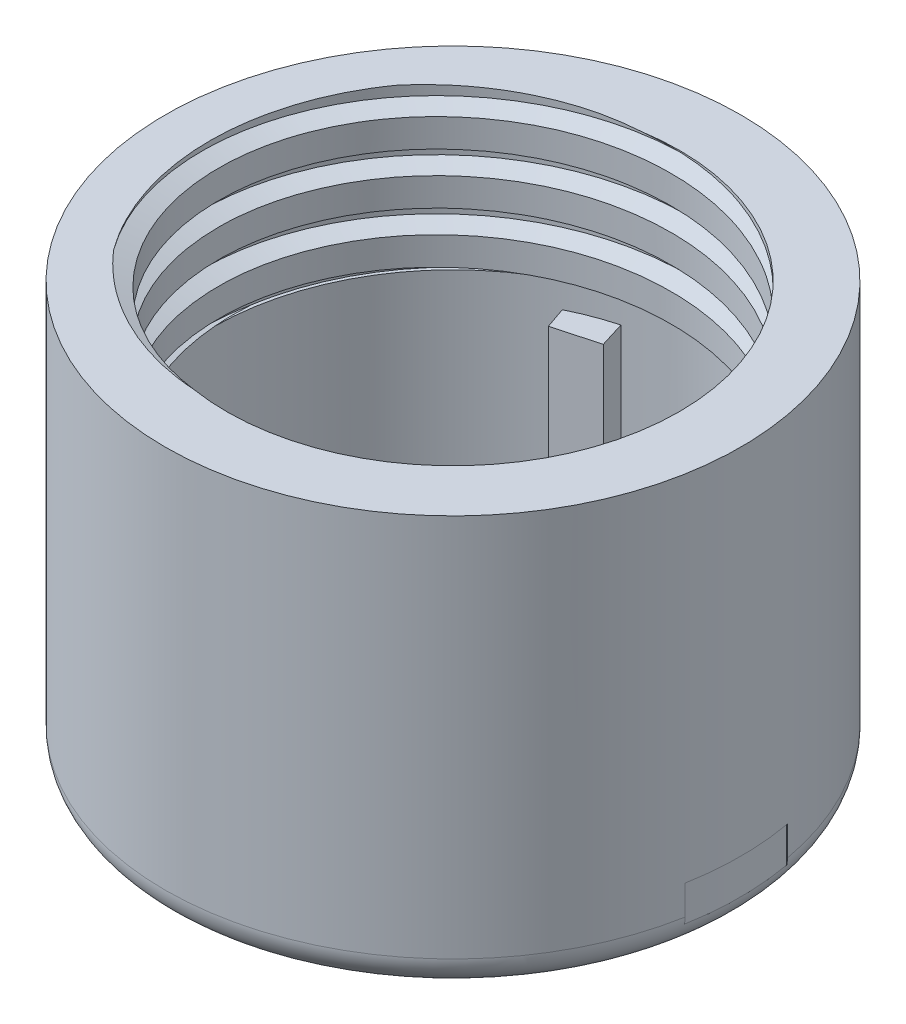
SolidWorks part; units mm, degrees
ref_plane "Front" through (0, 0, 0) normal (0, 0, 1) x (1, 0, 0)
ref_plane "Top" through (0, 0, 0) normal (0, 1, 0) x (1, 0, 0)
ref_plane "Right" through (0, 0, 0) normal (1, 0, 0) x (0, 0, -1)
sketch "Эскиз1" plane through (0, 0, 0) normal (0, 1, 0) x (1, 0, 0)
  circle A0 centre (0, 0) radius 22.5
extrude "Бобышка-Вытянуть1" add sketch "Эскиз1" along normal blind 1
sketch "Эскиз2" plane through (0, 1, 0) normal (0, 1, 0) x (1, 0, 0)
  circle A0 centre (0, 0) radius 22.5
  circle A1 centre (0, 0) radius 17.7
extrude "Бобышка-Вытянуть2" add sketch "Эскиз2" along normal blind 12.5
sketch "Эскиз4" plane through (0, 1, 0) normal (0, 1, 0) x (1, 0, 0)
  circle A0 centre (0, 0) radius 1.5
extrude "Вырез-Вытянуть1" cut sketch "Эскиз4" against normal through all
sketch "Эскиз9" plane through (0, 0, 0) normal (0, -1, 0) x (-1, 0, 0)
  circle A0 centre (0, 0) radius 22.5
  circle A1 centre (0, 0) radius 18.75
extrude "Бобышка-Вытянуть3" add sketch "Эскиз9" along normal blind 17
ref_plane "Плоскость1" through (0, 16.5, 0) normal (0, -1, 0) x (-1, 0, 0)
sketch "Эскиз10" plane through (0, 16.5, 0) normal (0, -1, 0) x (-1, 0, 0)
  circle A0 centre (0, 0) radius 17.7
curve "Спираль1" pitch 4 height 15.5 turns 3.875
sketch "Эскиз11" plane through (0, 16.5, 0) normal (0, -1, 0) x (-1, 0, 0)
  circle A0 centre (0, 0) radius 10 construction
ref_plane "Плоскость2" through (0, 0, 0) normal (-1, 0, 0) x (0, 0, 1)
sketch "Эскиз12" plane through (0, 0, 0) normal (-1, 0, 0) x (0, 0, 1)
  line L0 (-17.7, 17.4) -> (-17.7, 15.6)
  line L1 (-17.7, 16.5) -> (-19, 16.5) construction
  line L2 (-19, 16.1) -> (-17.7, 15.6)
  line L3 (-19, 16.1) -> (-19, 16.9)
  line L4 (-19, 16.9) -> (-17.7, 17.4)
  circle A0 centre (-17.7, 16.5) radius 0.9 construction
  circle A1 centre (-19, 16.5) radius 0.4 construction
sweep "Вырез-По траектории1" cut profiles "Эскиз12" path "Спираль1"
sketch "Эскиз13" plane through (0, 1, 0) normal (0, 1, 0) x (1, 0, 0)
  circle A0 centre (0, 0) radius 18.75 construction
  circle A1 centre (0, 0) radius 16.5 construction
  circle A2 centre (0, 16.5) radius 2
  circle A3 centre (0, -16.5) radius 2
hole_wizard "Зенковка для  винта с плоской головкой M21" positions "Трехмерный эскиз1" profile "Эскиз14" countersink size "M2" standard "Ansi Metric"
sketch3d "Трехмерный эскиз1"
  point P0 (0, 1, -16.5)
  point P3 (0, 1, 16.5)
sketch "Эскиз14" plane through (0, 1, -16.5) normal (1, 0, 0) x (0, 0, 1)
  line L0 (0, 0) -> (0, 18)
  line L1 (0, 18) -> (1.2, 18)
  line L2 (1.2, 18) -> (1.2, 1)
  line L3 (1.2, 1) -> (2.2, 0)
  line L5 (2.2, 0) -> (0, 0)
  line L6 (-1.2, 1) -> (-2.2, 0) construction
  line L11 (0, -6.35) -> (0, 107.95) construction
  dimension "Диаметр сквозного отверстия" = 2.4
  dimension "Глубина сквозного отверстия" = 18
  dimension "Диаметр передней зенковки" = 4.4
  dimension "Угол передней зенковки" = 90
sketch "Эскиз16" plane through (0, 1, 0) normal (0, 1, 0) x (1, 0, 0)
  circle A0 centre (0, 0) radius 18.75
extrude "Вырез-Вытянуть2" cut sketch "Эскиз16" against normal through all
sketch "Эскиз17" plane through (0, -17, 0) normal (0, -1, 0) x (1, 0, 0)
  circle A0 centre (0, 0) radius 22.5
extrude "Бобышка-Вытянуть4" add sketch "Эскиз17" along normal blind 2
fillet "Скругление1" radius 2.5 1 edges at (0, -19, -22.5)
sketch "Эскиз18" plane through (0, -17, 0) normal (0, 1, 0) x (1, 0, 0)
  line L0 (0, 0) -> (18.75, 0) construction
  line L1 (0, 0) -> (-11, 0) construction
ref_plane "Плоскость3" through (18.75, -17, 0) normal (1, 0, 0) x (0, 0, -1)
sketch "Эскиз19" plane through (18.75, -17, 0) normal (1, 0, 0) x (0, 0, -1)
  line L0 (0, 0) -> (0, 2.8) construction
  line L1 (-4, 0) -> (-4, 2.8)
  line L2 (-4, 0) -> (4, 0)
  line L3 (-4, 2.8) -> (4, 2.8)
  line L4 (4, 0) -> (4, 2.8)
  line L5 (-4, 0) -> (4, 2.8) construction
  line L6 (-4, 2.8) -> (4, 0) construction
  circle A0 centre (0, 0) radius 4 construction
  point P6 (0, 1.4)
extrude "Вырез-Вытянуть10" cut sketch "Эскиз19" against normal blind 2 and the other way blind 5
sketch "Эскиз20" plane through (18.75, -17, 0) normal (1, 0, 0) x (0, 0, -1)
  line L0 (0, 0) -> (0, 4.2) construction
  line L1 (8.8, 4.2521) -> (8.8, -0.0521)
  line L2 (8.8, 4.2521) -> (-8.8, 4.2521)
  line L3 (8.8, -0.0521) -> (-8.8, -0.0521)
  line L4 (-8.8, 4.2521) -> (-8.8, -0.0521)
  line L5 (8.8, 4.2521) -> (-8.8, -0.0521) construction
  line L6 (8.8, -0.0521) -> (-8.8, 4.2521) construction
  circle A0 centre (0, 0) radius 8.8 construction
  point P6 (0, 2.1)
extrude "Вырез-Вытянуть11" cut sketch "Эскиз20" against normal blind 2
sketch "Эскиз21" plane through (0, -17, 0) normal (0, 1, 0) x (1, 0, 0)
  circle A0 centre (-11, 0) radius 1.5
extrude "Вырез-Вытянуть12" cut sketch "Эскиз21" against normal blind 2
sketch "Эскиз22" plane through (0, -17, 0) normal (0, 1, 0) x (1, 0, 0)
  line L1 (0, 13.84) -> (2.0005, 14.995)
  line L2 (2.0005, 14.995) -> (2.0005, 17.305)
  line L3 (2.0005, 17.305) -> (0, 18.46)
  line L4 (0, 18.46) -> (-2.0005, 17.305)
  line L5 (-2.0005, 17.305) -> (-2.0005, 14.995)
  line L6 (-2.0005, 14.995) -> (0, 13.84)
  line L7 (0, -13.84) -> (-2.0005, -14.995)
  line L8 (-2.0005, -14.995) -> (-2.0005, -17.305)
  line L9 (-2.0005, -17.305) -> (0, -18.46)
  line L10 (0, -18.46) -> (2.0005, -17.305)
  line L11 (2.0005, -17.305) -> (2.0005, -14.995)
  line L12 (2.0005, -14.995) -> (0, -13.84)
  circle A0 centre (0, 0) radius 16.15 construction
  circle A1 centre (0, 16.15) radius 2.31 construction
  circle A2 centre (0, -16.15) radius 2.31 construction
  circle A3 centre (0, 16.15) radius 2.0005 construction
  circle A4 centre (0, -16.15) radius 2.0005 construction
  circle A5 centre (0, 16.15) radius 2.6 construction
  circle A6 centre (0, -16.15) radius 2.6 construction
  arc A7 (-4.9554, -18.0833) -> (4.9554, -18.0833) centre (0, 0) ccw
  circle A8 centre (0, 18.75) radius 5 construction
  arc A9 (-4.9554, 18.0833) -> (4.9554, 18.0833) centre (0, 18.525) ccw
  circle A10 centre (0, -18.75) radius 5 construction
  arc A11 (-4.9554, -18.0833) -> (4.9554, -18.0833) centre (0, -18.525) cw
  arc A12 (4.9554, 18.0833) -> (-4.9554, 18.0833) centre (0, 0) ccw
extrude "Бобышка-Вытянуть5" add sketch "Эскиз22" along normal blind 4
sketch "Эскиз23" plane through (0, -17, 0) normal (0, 1, 0) x (1, 0, 0)
  line L0 (-2.0005, 17.305) -> (2.0005, 14.995) construction
  line L1 (-2.0005, -14.995) -> (2.0005, -17.305) construction
  circle A0 centre (0, 16.15) radius 2.31
  circle A1 centre (0, 16.15) radius 1.15
  circle A2 centre (0, -16.15) radius 2.31
  circle A3 centre (0, -16.15) radius 1.15
extrude "Бобышка-Вытянуть6" add sketch "Эскиз23" along normal blind 2
sketch "Эскиз25" plane through (0, -17, 0) normal (0, 1, 0) x (1, 0, 0)
  line L0 (-4.9554, 18.0833) -> (-4.3342, 16.0826)
  line L1 (4.9554, 18.0833) -> (4.3342, 16.0826)
  line L2 (4.3342, 16.0826) -> (7.6502, 15.0531)
  line L3 (7.6502, 15.0531) -> (8.2788, 16.8233)
  line L4 (-4.3342, 16.0826) -> (-7.7047, 15.16)
  line L5 (-7.7047, 15.16) -> (-8.2788, 16.8233)
  line L6 (4.9554, -18.0833) -> (4.3342, -16.0826)
  line L7 (4.3342, -16.0826) -> (7.7047, -15.16)
  line L8 (7.7047, -15.16) -> (8.2788, -16.8233)
  line L9 (-4.9554, -18.0833) -> (-4.3342, -16.0826)
  line L10 (-4.3342, -16.0826) -> (-7.7047, -15.16)
  line L11 (-7.7047, -15.16) -> (-8.2788, -16.8233)
  circle A0 centre (0, 0) radius 18.75 construction
  circle A1 centre (0, 18.75) radius 8.5 construction
  circle A2 centre (6.1487, 15.885) radius 1.7165 construction
  circle A3 centre (-6.1487, 15.885) radius 1.7165 construction
  circle A4 centre (0, -18.75) radius 8.5 construction
  circle A5 centre (-6.1487, -15.885) radius 1.7165 construction
  circle A6 centre (6.1487, -15.885) radius 1.7165 construction
  arc A7 (-4.9554, 18.0833) -> (4.9554, 18.0833) centre (0, 18.525) ccw construction
  arc A8 (4.9554, 18.0833) -> (8.2788, 16.8233) centre (0, 0) cw
  arc A9 (-4.9554, 18.0833) -> (4.9554, 18.0833) centre (0, 18.525) ccw construction
  arc A10 (-8.2788, 16.8233) -> (-4.9554, 18.0833) centre (0, 0) cw
  arc A11 (4.9554, -18.0833) -> (-4.9554, -18.0833) centre (0, -18.525) ccw construction
  arc A12 (4.9554, -18.0833) -> (8.2788, -16.8233) centre (0, 0) ccw
  arc A13 (4.9554, -18.0833) -> (-4.9554, -18.0833) centre (0, -18.525) ccw construction
  arc A14 (-8.2788, -16.8233) -> (-4.9554, -18.0833) centre (0, 0) ccw
extrude "Бобышка-Вытянуть7" add sketch "Эскиз25" along normal blind 16
sketch "Эскиз26" plane through (0, -17, 0) normal (0, 1, 0) x (1, 0, 0)
  line L0 (22.0903, 4) -> (21.7903, 4)
  line L1 (22.0903, 4) -> (18.75, 4) construction
  line L2 (21.7903, 4) -> (21.7903, -4)
  line L3 (22.0903, -4) -> (18.75, -4) construction
  line L4 (21.7903, -4) -> (22.0903, -4)
  arc A0 (22.0903, 4) -> (22.0903, -4) centre (0, 0) cw
extrude "Бобышка-Вытянуть8" add sketch "Эскиз26" along normal up to surface (2.8 mm away) up to face at (20.5354, -14.2, 0)
